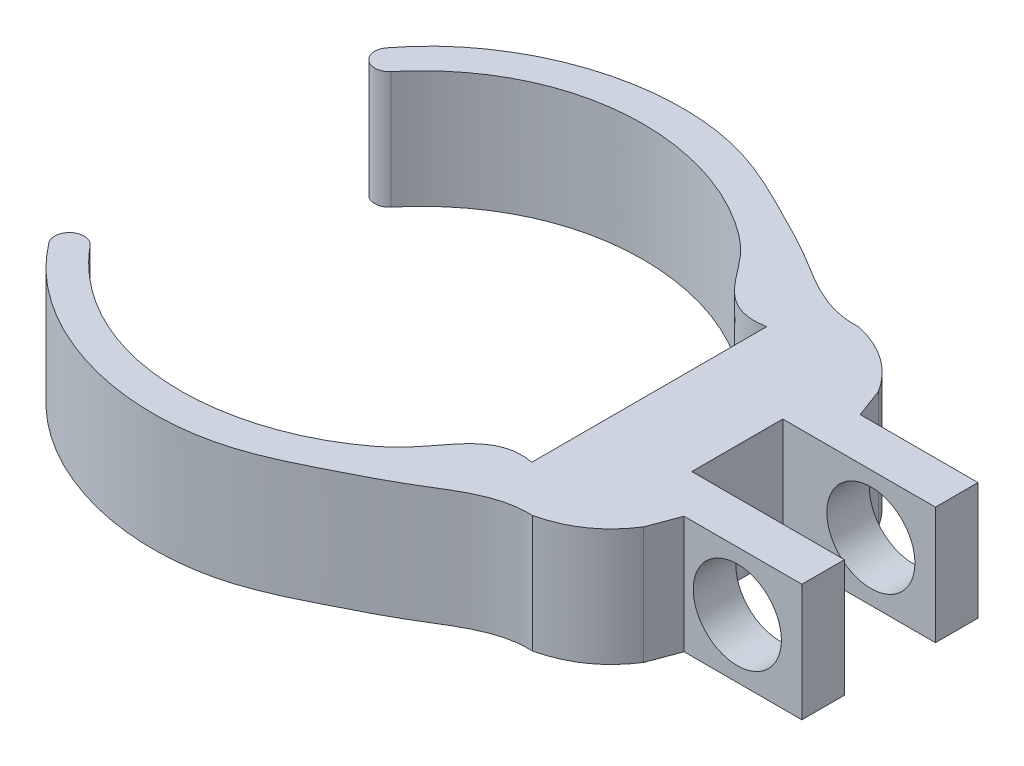
SolidWorks part; units mm, degrees
ref_plane "Front Plane" through (0, 0, 0) normal (0, 0, 1) x (1, 0, 0)
ref_plane "Top Plane" through (0, 0, 0) normal (0, 1, 0) x (1, 0, 0)
ref_plane "Right Plane" through (0, 0, 0) normal (1, 0, 0) x (0, 0, -1)
sketch "Sketch1" plane through (0, 0, 0) normal (0, 1, 0) x (1, 0, 0)
  line L0 (0, 4) -> (15, 4) construction
  line L1 (0, 0) -> (15, 0) construction
  line L2 (0, 0) -> (0, 8) construction
  line L3 (0, 8) -> (15, 8) construction
  line L4 (15, 0) -> (15, 8) construction
  line L5 (-13.9234, 9.1252) -> (-14.6796, 9.7795)
  line L6 (3, 2.45) -> (8.2, 2.45)
  line L7 (0, 8) -> (3, 8)
  line L8 (0, 8) -> (0, 0)
  line L9 (0, 0) -> (3, 0)
  line L10 (3, 8) -> (3, 0)
  line L11 (3, 8) -> (8.2, 8)
  line L12 (1.4624, 0) -> (1.5798, -1.5607)
  line L13 (3, 8) -> (3, 5.55)
  line L14 (3, 5.55) -> (8.2, 5.55)
  line L15 (8.2, 8) -> (8.2, 5.55)
  line L16 (8.2, 0) -> (8.2, 2.45)
  line L17 (3, 0) -> (8.2, 0)
  line L18 (3, 0) -> (3, 2.45)
  line L19 (3, 7) -> (8.2, 7)
  line L20 (3.8125, 8) -> (4.1858, 7)
  line L21 (3.8125, 0) -> (4.1858, 1)
  line L22 (3, 1) -> (8.2, 1)
  arc A2 (-14.6796, 9.7795) -> (-13.9234, 9.1252) centre (-14.3015, 9.4523) ccw
  circle A4 centre (-8, 4) radius 7.55 construction
  arc A5 (-14.6796, -1.7795) -> (-13.9234, -1.1252) centre (-14.3015, -1.4523) cw
  spline S0 degree 3 poles (0, 8) (-1.445, 7.7316) (-1.9898, 9.2748) (-5.9964, 12.5325) (-11.0436, 12.5964) (-13.9234, 9.1252) knots 0 0 0 0 0.216898 0.270831 1 1 1 1
  spline S1 degree 3 poles (0, 0) (-1.445, 0.2684) (-1.9898, -1.2748) (-5.9964, -4.5325) (-11.0436, -4.5964) (-13.9234, -1.1252) knots 0 0 0 0 0.216898 0.270831 1 1 1 1
  spline S2 degree 3 poles (-14.6796, 9.7795) (-12.6289, 12.4741) (-7.7143, 13.9514) (-3.3453, 11.7401) (-1.0056, 10.5602) (0.3946, 9.5012) (1.5798, 9.5607) knots 0 0 0 0 0.557353 0.711947 0.815566 1 1 1 1
  spline S3 degree 3 poles (-14.6796, -1.7795) (-12.6289, -4.4741) (-7.7143, -5.9514) (-3.3453, -3.7401) (-1.0056, -2.5602) (0.3946, -1.5012) (1.5798, -1.5607) knots 0 0 0 0 0.557353 0.711947 0.815566 1 1 1 1
  spline S4 degree 2 poles (1.5798, 9.5607) (3.0164, 9.232) (3.8125, 8) knots 0 0 0 1 1 1
  spline S5 degree 2 poles (1.5798, -1.5607) (3.0164, -1.232) (3.8125, 0) knots 0 0 0 1 1 1
  dimension "D3" = 3
  dimension "D4" = 15.1
  dimension "D5" = 4
  dimension "D6" = 8
  dimension "D1" = 15
  dimension "D2" = 8
  dimension "D7" = 1
  dimension "D8" = 1.55
  dimension "D9" = 5.2
  dimension "D10" = 1
extrude "Boss-Extrude1" add sketch "Sketch1" along normal blind 4 contours L4 | L4 L3 L2 L1 | L10 L22 L16 L6 | L22 L18 L17 L21 | L12 S5 L17 L9 | L10 L7 L8 L9 L18 L13 | L19 L13 L14 L15 | L20 L11 L10 L19 | S4 S2 L5 S0 L7 L11 | A5 S3 L12 L9 S1 | L5 A2 region at (1.5, 0, -4) region at (0.7312, 0, 0.1714) region at (2.3871, 0, 0.5956) region at (-6.7119, 0, -11.9523) region at (3.5054, 0, -0.5311) region at (3.5054, 0, -7.4689) region at (-14.4404, 0, -9.2918) region at (5.6, 0, -1.725) region at (5.6, 0, -6.275)
sketch "Sketch2" plane through (0, 0, -8) normal (0, 0, 1) x (1, 0, 0)
  line L0 (3, 4) -> (3, 0)
  line L14 (3, 0) -> (8.2, 0)
  line L15 (3, 4) -> (3, 0)
  line L16 (8.2, 4) -> (3, 4)
  line L17 (8.2, 0) -> (8.2, 4)
  line L18 (3, 0) -> (8.2, 0)
  line L20 (8.2, 4) -> (3, 4)
  line L21 (8.2, 0) -> (8.2, 4)
  circle A1 centre (6, 2) radius 1.5
  dimension "D2" = 0
  dimension "D3" = 3
  dimension "D4" = 2.2
extrude "Cut-Extrude1" cut sketch "Sketch2" along normal blind 10 contours A1 region at (6, 2, -8)
